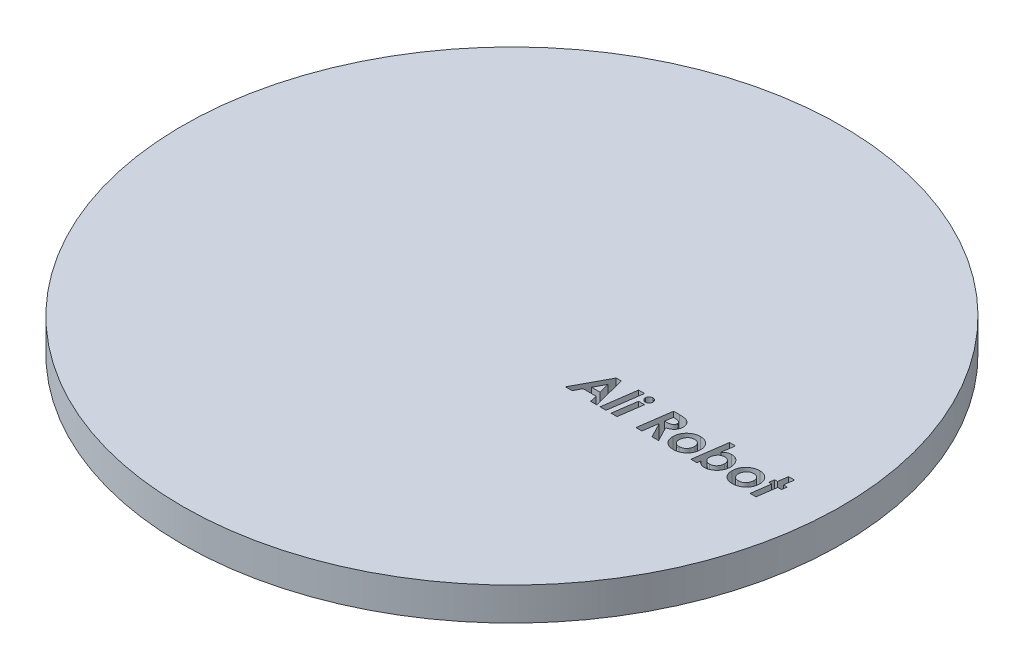
SolidWorks part; units mm, degrees
ref_plane "Front Plane" through (0, 0, 0) normal (0, 0, 1) x (1, 0, 0)
ref_plane "Top Plane" through (0, 0, 0) normal (0, 1, 0) x (1, 0, 0)
ref_plane "Right Plane" through (0, 0, 0) normal (1, 0, 0) x (0, 0, -1)
sketch "Sketch2" plane through (0, 0, 0) normal (0, 1, 0) x (1, 0, 0)
  circle A0 centre (0, 0) radius 35
  dimension "D1" = 70
extrude "Boss-Extrude1" add sketch "Sketch2" along normal blind 3.5
ref_plane "Plane1" through (-4, 0, 0) normal (1, 0, 0) x (0, 0, -1)
sketch "Sketch7" plane through (-4, 0, 0) normal (1, 0, 0) x (0, 0, -1)
  line L0 (18.6521, 16.3561) -> (18.6521, 3.5)
  line L5 (35, 3.5) -> (-35, 3.5) construction
  line L6 (-22.6311, 24.9401) -> (3.3119, 50.8831)
  line L7 (-43.5609, 3.5) -> (18.6521, 3.5)
  line L11 (-29.9535, 3.5) -> (-29.9535, 7.2624)
  arc A4 (24.252, 29.4036) -> (3.3119, 50.8831) centre (13.9185, 40.2765) ccw
  arc A5 (24.252, 29.4036) -> (18.6521, 16.3561) centre (36.6521, 16.3561) ccw
  arc A6 (-22.6311, 24.9401) -> (-29.9535, 7.2624) centre (-4.9535, 7.2624) ccw
  dimension "D1" = 25
  dimension "D4" = 30
  dimension "D3" = 18
  dimension "D5" = 45
sketch "Sketch33" plane through (0, 0, 0) normal (0, -1, 0) x (1, 0, 0)
  circle A0 centre (0, 0) radius 30
  dimension "D1" = 60
extrude "Boss-Extrude3" add sketch "Sketch33" along normal blind 2.2
ref_plane "Plane2" through (0, -4.2, 0) normal (0, -1, 0) x (-1, 0, 0)
sketch "Sketch35" plane through (64.9204, -4.2, -6.6124) normal (0, 1, 0) x (1, 0, 0)
  line L0 (-65.3345, -6.5857) -> (-65.3345, 41.3055) construction
  line L1 (-65.3345, -6.5857) -> (-104.6411, -6.5857) construction
  line L3 (-62.4345, -8.2857) -> (-68.2345, -8.2857)
  line L4 (-62.4345, -8.2857) -> (-62.4345, -4.8857)
  line L5 (-62.4345, -4.8857) -> (-68.2345, -4.8857)
  line L6 (-68.2345, -8.2857) -> (-68.2345, -4.8857)
  dimension "D1" = 3.4
  dimension "D2" = 5.8
  dimension "D3" = 1.7
  dimension "D4" = 2.9
sketch "Sketch37" plane through (0, 3.5, 0) normal (0, 1, 0) x (1, 0, 0)
  line L0 (-35, 0) -> (59.3455, 0) construction
  line L1 (0, -35) -> (0, 73.7974) construction
  circle A0 centre (0, 0) radius 35 construction
sketch "Sketch38" plane through (0, 3.5, 0) normal (0, 1, 0) x (1, 0, 0)
  text T0 "<b><i>Ali Robot</i></b>"
extrude "Cut-Extrude24" cut sketch "Sketch38" against normal blind 3
extrude "Boss-Extrude4" add sketch "Sketch35" against normal blind 6
shell "Shell2" thickness 1 removed face at (-0.4141, -10.2, -0.0268) outward yes
